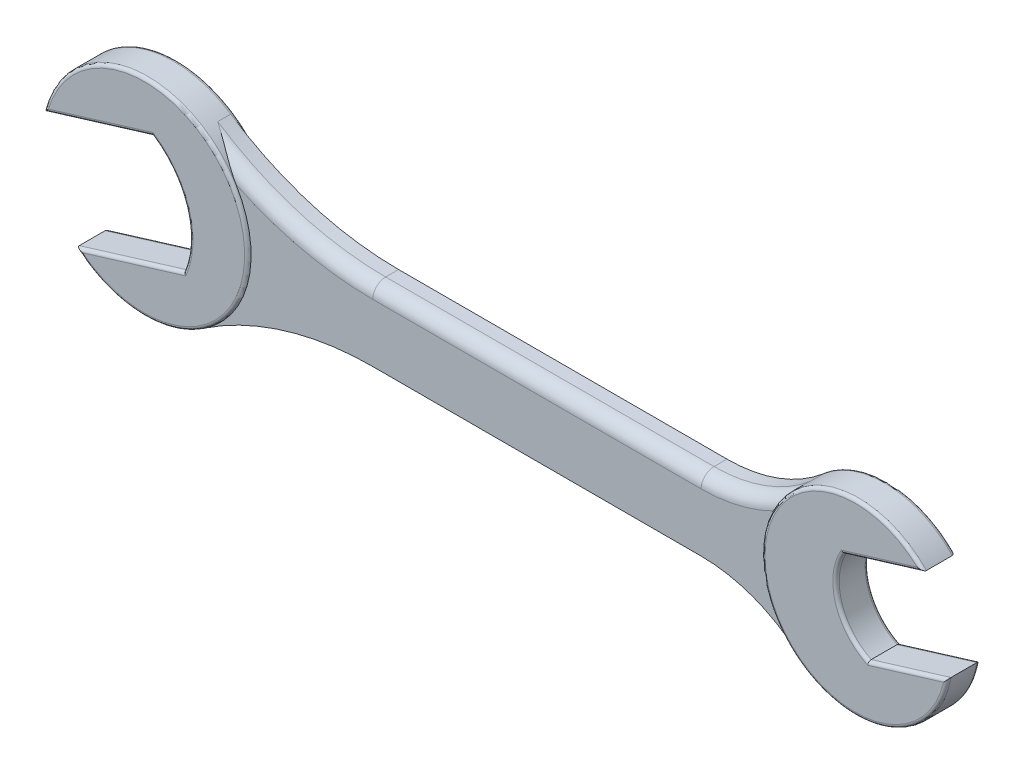
SolidWorks part; units mm, degrees
ref_plane "Front Plane" through (0, 0, 0) normal (0, 0, 1) x (1, 0, 0)
ref_plane "Top Plane" through (0, 0, 0) normal (0, 1, 0) x (1, 0, 0)
ref_plane "Right Plane" through (0, 0, 0) normal (1, 0, 0) x (0, 0, -1)
sketch "Sketch1" plane through (0, 0, 0) normal (0, 0, 1) x (1, 0, 0)
  line L0 (-55, 0) -> (55, 0) construction
  line L1 (-20.1754, 5.5) -> (30.6279, 5.5)
  line L2 (-20.1754, -5.5) -> (30.6279, -5.5)
  line L3 (-53.7735, 8.8064) -> (-70.5734, 3.6702)
  line L4 (-48.9661, -6.9179) -> (-65.5845, -11.9987)
  line L5 (-53.7735, 8.8064) -> (-48.9661, -6.9179) construction
  line L6 (-55, 0) -> (-84.2895, 0) construction
  line L7 (53.1466, 6.2304) -> (65.4947, 10.0056)
  line L8 (56.9475, -6.2016) -> (69.2955, -2.4264)
  line L9 (53.1466, 6.2304) -> (56.9475, -6.2016) construction
  line L10 (69.3459, 1.8344) -> (52.6541, 1.8344) construction
  line L11 (55, 0) -> (78.6014, 0) construction
  arc A0 (-65.5845, -11.9987) -> (-46.1557, -13.3333) centre (-55, 0) ccw
  arc A1 (65.4947, 10.0056) -> (45.5761, 11.02) centre (55, 0) ccw
  arc A2 (-53.7735, 8.8064) -> (-48.9661, -6.9179) centre (-61, -2) cw
  arc A3 (53.1466, 6.2304) -> (56.9475, -6.2016) centre (61, 1.8344) ccw
  arc A4 (-46.1557, 13.3333) -> (-70.5734, 3.6702) centre (-55, 0) ccw
  arc A5 (45.5761, -11.02) -> (69.2955, -2.4264) centre (55, 0) ccw
  arc A6 (-20.1754, -5.5) -> (-46.1557, -13.3333) centre (-20.1754, -52.5) ccw
  arc A7 (-20.1754, 5.5) -> (-46.1557, 13.3333) centre (-20.1754, 52.5) cw
  arc A8 (-46.1557, 13.3333) -> (-46.1557, -13.3333) centre (-55, 0) cw
  arc A9 (30.6279, -5.5) -> (45.5761, -11.02) centre (30.6279, -28.5) cw
  arc A10 (30.6279, 5.5) -> (45.5761, 11.02) centre (30.6279, 28.5) ccw
  arc A11 (45.5761, 11.02) -> (45.5761, -11.02) centre (55, 0) ccw
  point P4 (0, 0)
  point P17 (61, 1.8344)
  point P26 (-39.975, -5.5)
  point P29 (-39.975, 5.5)
  point P32 (41.5836, -5.5)
  point P35 (41.5836, 5.5)
  dimension "D1" = 32
  dimension "D2" = 29
  dimension "D7" = 13
  dimension "D12" = 9
  dimension "D14" = 47
  dimension "D15" = 23
  dimension "D3" = 110
  dimension "D4" = 11
  dimension "D5" = 6
  dimension "D6" = 2
  dimension "D8" = 16.4428
  dimension "D9" = 17
  dimension "D10" = 17
  dimension "D11" = 6
  dimension "D13" = 13
extrude "Boss-Extrude1" add sketch "Sketch1" along normal mid plane 5 contours A8 A4 L3 A2 L4 A0 | A1 A11 A5 L8 A3 L7 region at (-39.4495, 0, 0) region at (52.3723, -0.8034, 0)
extrude "Boss-Extrude2" add sketch "Sketch1<3>" along normal mid plane 4 contours A11 A10 L1 A7 A8 A6 L2 A9 region at (-0.9046, 0, 0)
sketch "Sketch1<3>" plane through (0, 0, 0) normal (0, 0, 1) x (1, 0, 0) same geometry as "Sketch1"
fillet "Fillet1" radius 2 6 edges at (-33.7432, 7.5009, 2) (38.5953, 6.9241, 2) (-33.7432, -7.5009, -2) (38.5953, -6.9241, -2) (5.2262, 5.5, 2) (5.2262, -5.5, -2)
fillet "Fillet2" radius 0.5 16 edges at (59.3207, 8.118, 2.5) (52.3933, -0.797, 2.5) (63.1215, -4.314, 2.5) (41.1336, -4.2394, 2.5) (-62.1735, 6.2383, -2.5) (-48.568, 1.8008, -2.5) (-57.2753, -9.4583, -2.5) (-39.7541, 4.8542, -2.5) (63.1215, -4.314, -2.5) (52.3933, -0.797, -2.5) (59.3207, 8.118, -2.5) (41.1336, -4.2394, -2.5) (-57.2753, -9.4583, 2.5) (-48.568, 1.8008, 2.5) (-62.1735, 6.2383, 2.5) (-39.7541, 4.8542, 2.5)
